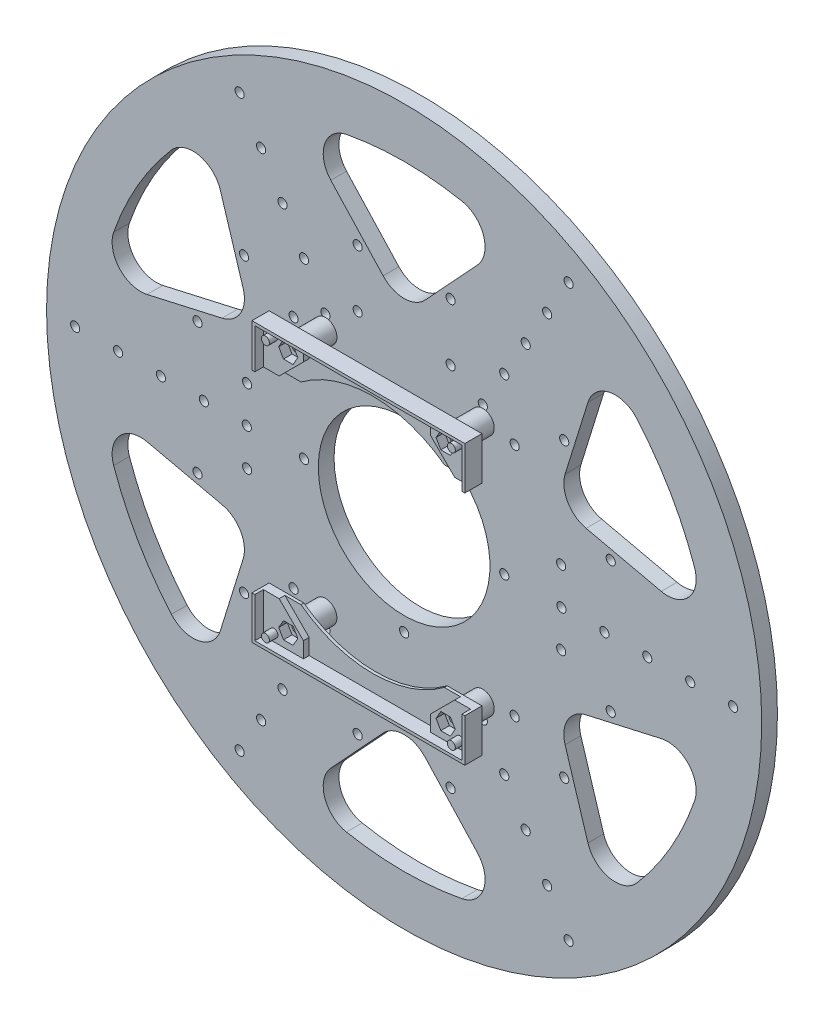
SolidWorks part; units mm, degrees
material "ﾎﾟﾘｴﾁﾚﾝﾃﾚﾌﾀﾗｰﾄ(PET)"
ref_plane "正面" through (0, 0, 0) normal (0, 0, 1) x (1, 0, 0)
ref_plane "平面" through (0, 0, 0) normal (0, 1, 0) x (1, 0, 0)
ref_plane "右側面" through (0, 0, 0) normal (1, 0, 0) x (0, 0, -1)
sketch "ｽｹｯﾁ1" plane through (0, 0, 0) normal (0, 0, 1) x (1, 0, 0)
  circle A0 centre (0, 0) radius 125
  dimension "D1" = 250
extrude "ﾎﾞｽ - 押し出し1" add sketch "ｽｹｯﾁ1" along normal blind 5.5
sketch "ｽｹｯﾁ2" plane through (0, 0, 0) normal (0, 1, 0) x (1, 0, 0)
  line L0 (0, 0) -> (0, -50)
  dimension "D1" = 50
sketch "ｽｹｯﾁ3" plane through (0, 0, 0) normal (0, 0, -1) x (-1, 0, 0)
  line L0 (0, 0) -> (0, 64) construction
  line L1 (0, 0) -> (0, 76) construction
  line L2 (16.25, 54) -> (-16.25, 54) construction
  line L3 (16.25, 54) -> (16.25, 74) construction
  line L4 (16.25, 74) -> (-16.25, 74) construction
  line L5 (-16.25, 54) -> (-16.25, 74) construction
  line L6 (16.25, 54) -> (-16.25, 74) construction
  line L7 (16.25, 74) -> (-16.25, 54) construction
  line L8 (0, 107.5) -> (0, 0) construction
  line L9 (0, 0) -> (36.7672, 101.017) construction
  line L10 (0, 0) -> (-36.7672, 101.017) construction
  line L11 (-25.6298, 88.9783) -> (-7.3405, 69.209)
  line L12 (25.6298, 88.9783) -> (7.3405, 69.209)
  circle A0 centre (-16.25, 74) radius 1.6
  circle A1 centre (-16.25, 54) radius 1.6
  circle A2 centre (16.25, 54) radius 1.6
  circle A3 centre (16.25, 74) radius 1.6
  circle A4 centre (0, 76) radius 10 construction
  circle A5 centre (0, 0) radius 107.5 construction
  arc A6 (-20.1651, 105.5918) -> (20.1651, 105.5918) centre (0, 0) cw
  arc A7 (-7.3405, 69.209) -> (7.3405, 69.209) centre (0, 76) ccw
  arc A8 (-25.6298, 88.9783) -> (-20.1651, 105.5918) centre (-18.2893, 95.7693) cw
  arc A9 (20.1651, 105.5918) -> (25.6298, 88.9783) centre (18.2893, 95.7693) cw
  dimension "D4" = 3.2
  dimension "D6" = 20
  dimension "D7" = 215
  dimension "D10" = 10
  dimension "D1" = 54
  dimension "D2" = 32.5
  dimension "D3" = 20
  dimension "D5" = 76
  dimension "D8" = 20
  dimension "D9" = 20
extrude "ｶｯﾄ - 押し出し1" cut sketch "ｽｹｯﾁ3" against normal through all
pattern_circular "円形ﾊﾟﾀｰﾝ1" count 6 over 360 about axis through (0, 0, 0) along (0, 0, 1) of "ｶｯﾄ - 押し出し1"
sketch "ｽｹｯﾁ4" plane through (0, 0, 0) normal (0, 0, -1) x (-1, 0, 0)
  circle A0 centre (0, 0) radius 30
  circle A1 centre (0, 0) radius 35 construction
  circle A2 centre (0, 35) radius 1.6
  circle A3 centre (35, 0) radius 1.6
  circle A4 centre (0, -35) radius 1.6
  circle A5 centre (-35, 0) radius 1.6
  point P15 (0, 0)
  dimension "D1" = 60
  dimension "D2" = 70
  dimension "D3" = 3.2
  dimension "D4" = 4
extrude "ｶｯﾄ - 押し出し2" cut sketch "ｽｹｯﾁ4" against normal through all
sketch "ｽｹｯﾁ5" plane through (0, 0, 0) normal (0, 0, -1) x (-1, 0, 0)
  line L1 (27.5, -42.5) -> (-27.5, -42.5) construction
  line L2 (27.5, -42.5) -> (27.5, 42.5) construction
  line L3 (27.5, 42.5) -> (-27.5, 42.5) construction
  line L4 (-27.5, -42.5) -> (-27.5, 42.5) construction
  line L5 (27.5, -42.5) -> (-27.5, 42.5) construction
  line L6 (27.5, 42.5) -> (-27.5, -42.5) construction
  circle A0 centre (-27.5, 42.5) radius 1.6
  circle A1 centre (27.5, 42.5) radius 1.6
  circle A2 centre (-27.5, -42.5) radius 1.6
  circle A3 centre (27.5, -42.5) radius 1.6
  point P0 (0, 0)
  dimension "D3" = 3.2
  dimension "D1" = 55
  dimension "D2" = 85
extrude "ｶｯﾄ - 押し出し3" cut sketch "ｽｹｯﾁ5" against normal through all
sketch "ｽｹｯﾁ6" plane through (0, 0, 0) normal (0, 0, -1) x (-1, 0, 0)
  line L0 (-115, 0) -> (0, 0) construction
  line L1 (-57.5, 99.5929) -> (0, 0) construction
  line L2 (57.5, 99.5929) -> (0, 0) construction
  line L3 (115, 0) -> (0, 0) construction
  line L4 (57.5, -99.5929) -> (0, 0) construction
  line L5 (-57.5, -99.5929) -> (0, 0) construction
  circle A0 centre (0, 0) radius 115 construction
  circle A1 centre (-115, 0) radius 1.6
  circle A2 centre (0, 0) radius 125 construction
  circle A3 centre (-100, 0) radius 1.6
  circle A4 centre (-85, 0) radius 1.6
  circle A5 centre (-70, 0) radius 1.6
  circle A6 centre (-55, 0) radius 1.6
  circle A7 centre (-57.5, 99.5929) radius 1.6
  circle A8 centre (-50, 86.6025) radius 1.6
  circle A9 centre (-42.5, 73.6122) radius 1.6
  circle A10 centre (-35, 60.6218) radius 1.6
  circle A11 centre (-27.5, 47.6314) radius 1.6
  circle A12 centre (57.5, 99.5929) radius 1.6
  circle A13 centre (50, 86.6025) radius 1.6
  circle A14 centre (42.5, 73.6122) radius 1.6
  circle A15 centre (35, 60.6218) radius 1.6
  circle A16 centre (27.5, 47.6314) radius 1.6
  circle A17 centre (115, 0) radius 1.6
  circle A18 centre (100, 0) radius 1.6
  circle A19 centre (85, 0) radius 1.6
  circle A20 centre (70, 0) radius 1.6
  circle A21 centre (55, 0) radius 1.6
  circle A22 centre (57.5, -99.5929) radius 1.6
  circle A23 centre (50, -86.6025) radius 1.6
  circle A24 centre (42.5, -73.6122) radius 1.6
  circle A25 centre (35, -60.6218) radius 1.6
  circle A26 centre (27.5, -47.6314) radius 1.6
  circle A27 centre (-57.5, -99.5929) radius 1.6
  circle A28 centre (-50, -86.6025) radius 1.6
  circle A29 centre (-42.5, -73.6122) radius 1.6
  circle A30 centre (-35, -60.6218) radius 1.6
  circle A31 centre (-27.5, -47.6314) radius 1.6
  point P68 (0, 0)
  dimension "D1" = 3.2
  dimension "D2" = 10
  dimension "D3" = 5
  dimension "D4" = 15
  dimension "D5" = 6
extrude "ｶｯﾄ - 押し出し4" cut sketch "ｽｹｯﾁ6" against normal through all
sketch "ｽｹｯﾁ7" plane through (0, 0, 5.5) normal (0, 0, -1) x (-1, 0, 0)
  circle A0 centre (-27.5, -42.5) radius 1.8
  circle A1 centre (27.5, -42.5) radius 1.8
  circle A2 centre (27.5, 42.5) radius 1.8
  circle A3 centre (-27.5, 42.5) radius 1.8
  circle A4 centre (-27.5, 42.5) radius 4
  circle A5 centre (27.5, 42.5) radius 4
  circle A6 centre (-27.5, -42.5) radius 4
  circle A7 centre (27.5, -42.5) radius 4
  dimension "D1" = 3.6
  dimension "D2" = 8
extrude "ﾎﾞｽ - 押し出し2" add sketch "ｽｹｯﾁ7" against normal blind 10 separate body
sketch "ｽｹｯﾁ8" plane through (0, 0, 15.5) normal (0, 0, 1) x (1, 0, 0)
  line L0 (37.2, -48.7) -> (-37.2, -48.7)
  line L1 (36, -47.5) -> (-36, -47.5) construction
  line L2 (36, -47.5) -> (36, 47.5) construction
  line L3 (36, 47.5) -> (-36, 47.5) construction
  line L4 (-36, -47.5) -> (-36, 47.5) construction
  line L5 (36, -47.5) -> (-36, 47.5) construction
  line L6 (36, 47.5) -> (-36, -47.5) construction
  line L7 (32.5, -45) -> (-32.5, -45) construction
  line L8 (32.5, -45) -> (32.5, 45) construction
  line L9 (32.5, 45) -> (-32.5, 45) construction
  line L10 (-32.5, -45) -> (-32.5, 45) construction
  line L11 (32.5, -45) -> (-32.5, 45) construction
  line L12 (32.5, 45) -> (-32.5, -45) construction
  line L13 (-37.2, -48.7) -> (-37.2, 48.7) construction
  line L14 (37.2, 48.7) -> (-37.2, 48.7)
  line L15 (37.2, -48.7) -> (37.2, 48.7) construction
  line L16 (-37.2, 48.7) -> (-37.2, 33.7)
  line L17 (-37.2, 33.7) -> (-25.0661, 33.7)
  line L18 (25.0661, 33.7) -> (37.2, 33.7)
  line L19 (37.2, 33.7) -> (37.2, 48.7)
  line L20 (3.025, 0) -> (-3.025, 0) construction
  line L21 (37.2, -33.7) -> (37.2, -48.7)
  line L22 (25.0661, -33.7) -> (37.2, -33.7)
  line L23 (-37.2, -33.7) -> (-25.0661, -33.7)
  line L24 (-37.2, -48.7) -> (-37.2, -33.7)
  arc A0 (-25.0661, 33.7) -> (25.0661, 33.7) centre (0, 0) cw
  arc A1 (-25.0661, -33.7) -> (25.0661, -33.7) centre (0, 0) ccw
  point P0 (0, 0)
  point P6 (0, 0)
  point P20 (-23.7813, 34.6186)
  dimension "D6" = 42
  dimension "D1" = 95
  dimension "D2" = 72
  dimension "D3" = 65
  dimension "D4" = 90
  dimension "D7" = 15
  dimension "D5" = 1.2
extrude "ﾎﾞｽ - 押し出し3" add sketch "ｽｹｯﾁ8" along normal blind 1
sketch "ｽｹｯﾁ10" plane through (0, 0, 16.5) normal (0, 0, 1) x (1, 0, 0)
  line L0 (37.2, 33.7) -> (37.2, 48.7) construction
  line L1 (37.2, 48.7) -> (-37.2, 48.7) construction
  line L2 (-37.2, 48.7) -> (-37.2, 33.7) construction
  line L3 (37.2, 33.7) -> (37.2, 48.7)
  line L4 (37.2, 48.7) -> (-37.2, 48.7)
  line L5 (-37.2, 48.7) -> (-37.2, 33.7)
  line L6 (36.2, 33.7) -> (36.2, 47.7)
  line L7 (36.2, 47.7) -> (-36.2, 47.7)
  line L8 (-36.2, 47.7) -> (-36.2, 33.7)
  line L9 (-37.2, 33.7) -> (-36.2, 33.7)
  line L10 (36.2, 33.7) -> (37.2, 33.7)
  line L11 (3.025, 0) -> (-3.025, 0) construction
  line L12 (36.2, -33.7) -> (37.2, -33.7)
  line L13 (-37.2, -33.7) -> (-36.2, -33.7)
  line L14 (-36.2, -47.7) -> (-36.2, -33.7)
  line L15 (36.2, -47.7) -> (-36.2, -47.7)
  line L16 (36.2, -33.7) -> (36.2, -47.7)
  line L17 (-37.2, -48.7) -> (-37.2, -33.7)
  line L18 (37.2, -48.7) -> (-37.2, -48.7)
  line L19 (37.2, -33.7) -> (37.2, -48.7)
  dimension "D1" = 1
extrude "ﾎﾞｽ - 押し出し4" add sketch "ｽｹｯﾁ10" along normal blind 5
sketch "ｽｹｯﾁ11" plane through (0, 0, 16.5) normal (0, 0, 1) x (1, 0, 0)
  line L0 (-36.2, 47.7) -> (-36.2, 33.7)
  line L1 (-36.2, 33.7) -> (-30.6853, 33.7)
  line L2 (-37.2, 33.7) -> (-25.0661, 33.7) construction
  line L3 (-36.2, 47.7) -> (-22.2, 47.7)
  line L4 (-36.2, 47.7) -> (36.2, 47.7) construction
  line L5 (-22.2, 47.7) -> (-22.2, 42.1853)
  line L6 (-22.2, 42.1853) -> (-30.6853, 33.7)
  line L7 (0, -3.025) -> (0, 3.025) construction
  line L8 (22.2, 42.1853) -> (30.6853, 33.7)
  line L9 (22.2, 47.7) -> (22.2, 42.1853)
  line L10 (36.2, 47.7) -> (22.2, 47.7)
  line L11 (36.2, 33.7) -> (30.6853, 33.7)
  line L12 (36.2, 47.7) -> (36.2, 33.7)
  line L13 (3.025, 0) -> (-3.025, 0) construction
  line L14 (36.2, -47.7) -> (36.2, -33.7)
  line L15 (36.2, -33.7) -> (30.6853, -33.7)
  line L16 (36.2, -47.7) -> (22.2, -47.7)
  line L17 (22.2, -47.7) -> (22.2, -42.1853)
  line L18 (22.2, -42.1853) -> (30.6853, -33.7)
  line L19 (-22.2, -42.1853) -> (-30.6853, -33.7)
  line L20 (-22.2, -47.7) -> (-22.2, -42.1853)
  line L21 (-36.2, -47.7) -> (-22.2, -47.7)
  line L22 (-36.2, -33.7) -> (-30.6853, -33.7)
  line L23 (-36.2, -47.7) -> (-36.2, -33.7)
  dimension "D1" = 12
extrude "ﾎﾞｽ - 押し出し5" add sketch "ｽｹｯﾁ11" along normal blind 2
sketch "ｽｹｯﾁ12" plane through (0, 0, 18.5) normal (0, 0, 1) x (1, 0, 0)
  circle A0 centre (-32.5, 45) radius 1.4
  circle A1 centre (32.5, 45) radius 1.4
  circle A2 centre (-32.5, -45) radius 1.4
  circle A3 centre (32.5, -45) radius 1.4
  dimension "D1" = 2.8
extrude "ﾎﾞｽ - 押し出し6" add sketch "ｽｹｯﾁ12" along normal blind 3
sketch "ｽｹｯﾁ13" plane through (0, 0, 15.5) normal (0, 0, -1) x (-1, 0, 0)
  line L1 (-29.1743, 39.6) -> (-25.8257, 39.6)
  line L2 (-25.8257, 39.6) -> (-24.1514, 42.5)
  line L3 (-24.1514, 42.5) -> (-25.8257, 45.4)
  line L4 (-25.8257, 45.4) -> (-29.1743, 45.4)
  line L5 (-29.1743, 45.4) -> (-30.8486, 42.5)
  line L6 (-30.8486, 42.5) -> (-29.1743, 39.6)
  line L7 (24.1514, 42.5) -> (25.8257, 39.6)
  line L8 (25.8257, 39.6) -> (29.1743, 39.6)
  line L9 (29.1743, 39.6) -> (30.8486, 42.5)
  line L10 (30.8486, 42.5) -> (29.1743, 45.4)
  line L11 (29.1743, 45.4) -> (25.8257, 45.4)
  line L12 (25.8257, 45.4) -> (24.1514, 42.5)
  line L13 (25.8257, -45.4) -> (29.1743, -45.4)
  line L14 (29.1743, -45.4) -> (30.8486, -42.5)
  line L15 (30.8486, -42.5) -> (29.1743, -39.6)
  line L16 (29.1743, -39.6) -> (25.8257, -39.6)
  line L17 (25.8257, -39.6) -> (24.1514, -42.5)
  line L18 (24.1514, -42.5) -> (25.8257, -45.4)
  line L19 (-30.8486, -42.5) -> (-29.1743, -45.4)
  line L20 (-29.1743, -45.4) -> (-25.8257, -45.4)
  line L21 (-25.8257, -45.4) -> (-24.1514, -42.5)
  line L22 (-24.1514, -42.5) -> (-25.8257, -39.6)
  line L23 (-25.8257, -39.6) -> (-29.1743, -39.6)
  line L24 (-29.1743, -39.6) -> (-30.8486, -42.5)
  circle A0 centre (-27.5, 42.5) radius 2.9 construction
  circle A1 centre (27.5, 42.5) radius 2.9 construction
  circle A2 centre (27.5, -42.5) radius 2.9 construction
  circle A3 centre (-27.5, -42.5) radius 2.9 construction
  point P28 (0, 0)
  dimension "D1" = 5.8
extrude "ｶｯﾄ - 押し出し5" cut sketch "ｽｹｯﾁ13" against normal through all
equation "\"D1@ｽｹｯﾁ3\"=50+4"
equation "\"D7@ｽｹｯﾁ3\"=107.5*2"
equation "\"D9@ｽｹｯﾁ3\"=\"D8@ｽｹｯﾁ3\""
